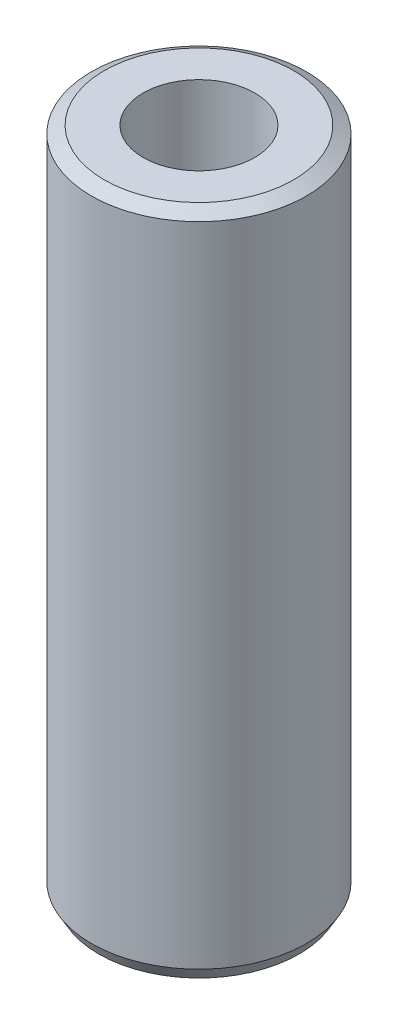
SolidWorks part; units mm, degrees
ref_plane "Front Plane" through (0, 0, 0) normal (0, 0, 1) x (1, 0, 0)
ref_plane "Top Plane" through (0, 0, 0) normal (0, 1, 0) x (1, 0, 0)
ref_plane "Right Plane" through (0, 0, 0) normal (1, 0, 0) x (0, 0, -1)
sketch "Sketch1" plane through (0, 0, 0) normal (0, 1, 0) x (1, 0, 0)
  circle A0 centre (0, 0) radius 35
  dimension "SHAFT_OD" = 70
extrude "Boss-Extrude1" add sketch "Sketch1" along normal blind 217.2057
sketch "Sketch2" plane through (0, 0, 0) normal (0, 1, 0) x (1, 0, 0)
  circle A0 centre (0, 0) radius 18.1811
  dimension "BORE_D" = 36.3623
extrude "Cut-Extrude1" cut sketch "Sketch2" along normal through all
chamfer "Chamfer1" distance 2.4255 angle 60 2 edges at (0, 217.2057, 35) (0, 0, 35) first distance on face at (0, 217.2057, 35) first distance on face at (0, 0, 18.1811)
